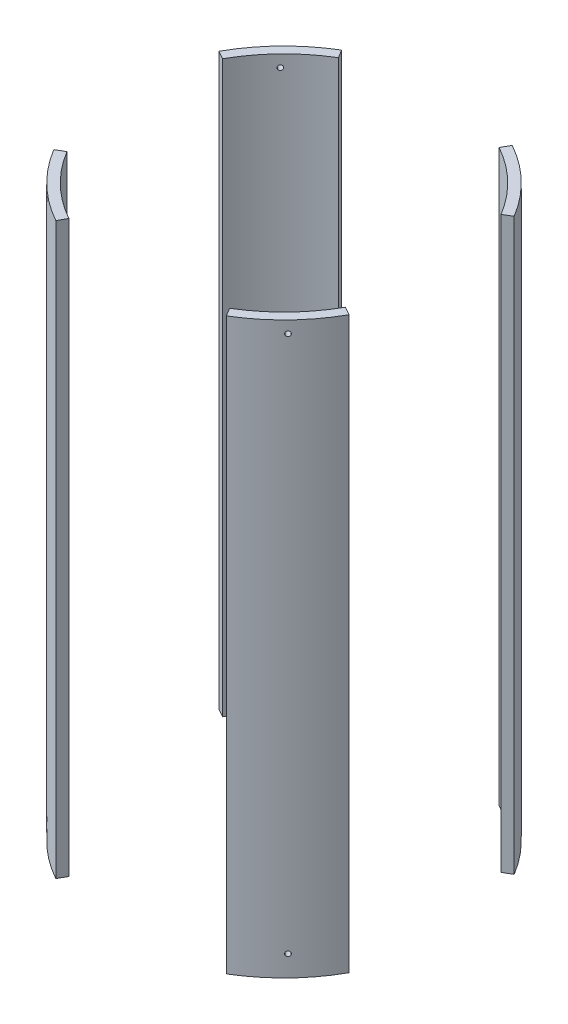
SolidWorks part; units mm, degrees
material "6061-T6 (SS)"
ref_plane "Front Plane" through (0, 0, 0) normal (0, 0, 1) x (1, 0, 0)
ref_plane "Top Plane" through (0, 0, 0) normal (0, 1, 0) x (1, 0, 0)
ref_plane "Right Plane" through (0, 0, 0) normal (1, 0, 0) x (0, 0, -1)
sketch "Sketch2" plane through (0, 0, 0) normal (0, 1, 0) x (1, 0, 0)
  circle A0 centre (0, 0) radius 88.9
  circle A1 centre (0, 0) radius 83.82
  dimension "D1" = 177.8
  dimension "D2" = 167.64
extrude "Boss-Extrude1" add sketch "Sketch2" along normal mid plane 301.9527
sketch "Sketch3" plane through (0, 0, 0) normal (0, 1, 0) x (1, 0, 0)
  line L0 (0, 0) -> (169.6618, 101.6776)
  line L1 (-58.1167, 96.9749) -> (0, 0)
  line L2 (0, 0) -> (53.9, 96.9749)
  line L3 (53.9, 96.9749) -> (-58.1167, 96.9749)
  line L4 (0, 0) -> (70.9917, -118.4586)
  line L5 (70.9917, -118.4586) -> (-65.8409, -118.4586)
  line L6 (-65.8409, -118.4586) -> (0, 0)
  line L7 (169.6618, 101.6776) -> (169.6618, -94.3004)
  line L8 (169.6618, -94.3004) -> (0, 0)
  line L9 (0, 0) -> (-123.7413, 68.7771)
  line L10 (-123.7413, 68.7771) -> (-123.7413, -74.1577)
  line L11 (-123.7413, -74.1577) -> (0, 0)
  dimension "D1" = 60
  dimension "D2" = 60
  dimension "D3" = 60
  dimension "D4" = 60
  dimension "D5" = 30
  dimension "D6" = 30
extrude "Cut-Extrude1" cut sketch "Sketch3" against normal through all both and the other way through all contours L8 L7 L0 | L2 L3 L1 | L10 L11 L9 | L6 L5 L4 region at (-1.4056, 0, -64.65) region at (1.7169, 0, 78.9724) region at (113.1078, 0, -2.4591) region at (-82.4942, 0, 1.7935)
ref_plane "Bolt reference plane" through (-56.3092, 0, 58.1758) normal (0.6955, 0, -0.7185) x (-0.7185, 0, -0.6955)
sketch "Sketch5" plane through (-56.3092, 0, 58.1758) normal (0.6955, 0, -0.7185) x (-0.7185, 0, -0.6955)
  line L0 (-23.009, -150.9763) -> (23.009, -150.9763) construction
  circle A0 centre (-0.0228, 144.6263) radius 1.27
  circle A1 centre (-0.0228, -139.8638) radius 1.27
  dimension "D1" = 2.54
  dimension "D4" = 11.1125
  dimension "D2" = 21.717
  dimension "D3" = 6.35
extrude "Bolt holes" cut sketch "Sketch5" against normal through all
pattern_circular "Bolt pattern" count 4 over 360 about axis through (0, 150.9763, 0) along (0, 1, 0) of "Bolt holes"
equation "\"D1@Boss-Extrude1\"=3*12"
